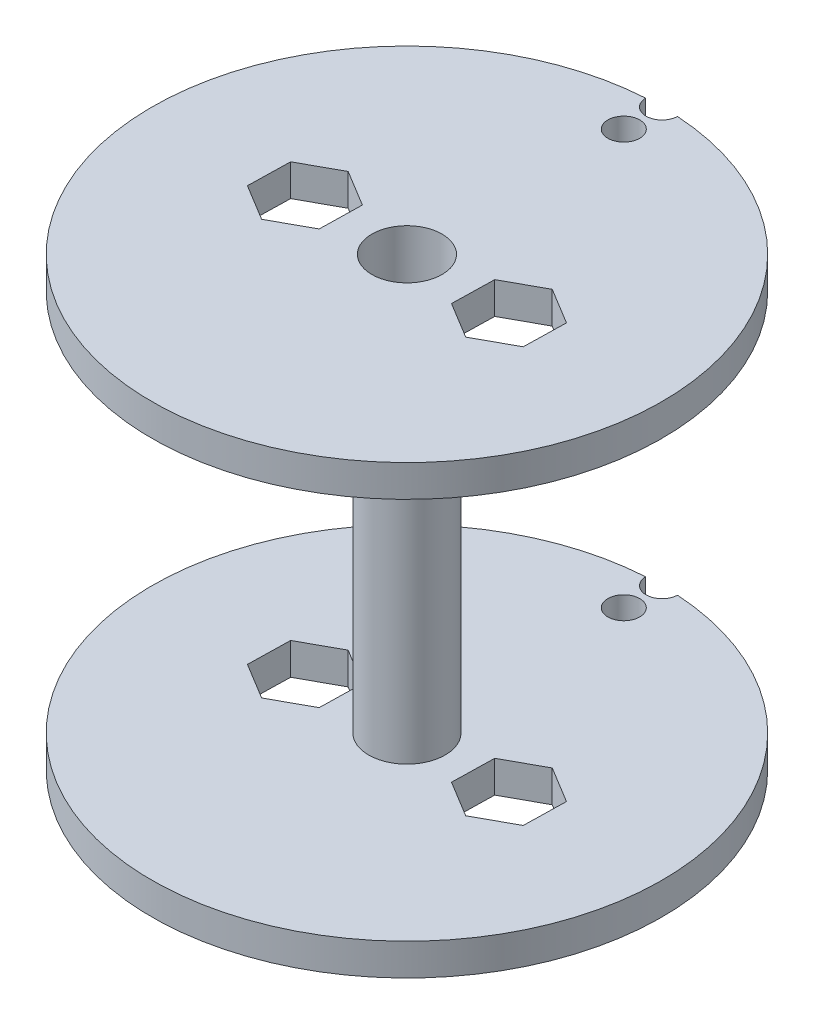
SolidWorks part; units mm, degrees
ref_plane "Front Plane" through (0, 0, 0) normal (0, 0, 1) x (1, 0, 0)
ref_plane "Top Plane" through (0, 0, 0) normal (0, 1, 0) x (1, 0, 0)
ref_plane "Right Plane" through (0, 0, 0) normal (1, 0, 0) x (0, 0, -1)
sketch "Sketch1" plane through (0, 0, 0) normal (0, 1, 0) x (1, 0, 0)
  circle A1 centre (0, 0) radius 20
  circle A2 centre (0, 0) radius 2.75
extrude "Boss-Extrude1" add sketch "Sketch1" along normal blind 2.5
sketch "Sketch2" plane through (0, 2.5, 0) normal (0, 1, 0) x (1, 0, 0)
  circle A0 centre (0, 0) radius 3
  circle A1 centre (0, 0) radius 2.75
sketch "Sketch3" plane through (0, 0, 0) normal (0, -1, 0) x (1, 0, 0)
  line L0 (-5.1613, 1.7213) -> (-8.0713, 3.319)
  line L1 (5.1613, -1.7213) -> (8.0713, -3.319)
  line L2 (8.0713, -3.319) -> (10.91, -1.5977)
  line L3 (10.91, -1.5977) -> (10.8387, 1.7213)
  line L4 (10.8387, 1.7213) -> (7.9287, 3.319)
  line L5 (7.9287, 3.319) -> (5.09, 1.5977)
  line L6 (5.09, 1.5977) -> (5.1613, -1.7213)
  line L7 (-8.0713, 3.319) -> (-10.91, 1.5977)
  line L8 (-10.91, 1.5977) -> (-10.8387, -1.7213)
  line L9 (-10.8387, -1.7213) -> (-7.9287, -3.319)
  line L10 (-7.9287, -3.319) -> (-5.09, -1.5977)
  line L11 (-5.09, -1.5977) -> (-5.1613, 1.7213)
  circle A0 centre (8, 0) radius 2.875 construction
  point P17 (0, 0)
  dimension "D2" = 8
  dimension "D1" = 2
extrude "Cut-Extrude3" cut sketch "Sketch3" against normal blind 2.5
sketch "Sketch4" plane through (0, 2.5, 0) normal (0, 1, 0) x (1, 0, 0)
  circle A0 centre (0, 17) radius 1.25
  circle A1 centre (0, 20) radius 1.25
  circle A2 centre (0, 0) radius 20 construction
  dimension "D1" = 17
extrude "Cut-Extrude4" cut sketch "Sketch4" against normal blind 5
sketch "Sketch5" plane through (0, 2.5, 0) normal (0, 1, 0) x (1, 0, 0)
  circle A0 centre (0, -16.2068) radius 3.1
extrude "Cut-Extrude5" [suppressed] cut sketch "Sketch5" along normal blind 2.5 from surface
extrude "Boss-Extrude2" add sketch "Sketch2" along normal blind 15
mirror "Mirror7" about plane through (0, 17.5, 0) normal (0, 1, 0) of bodies 107
